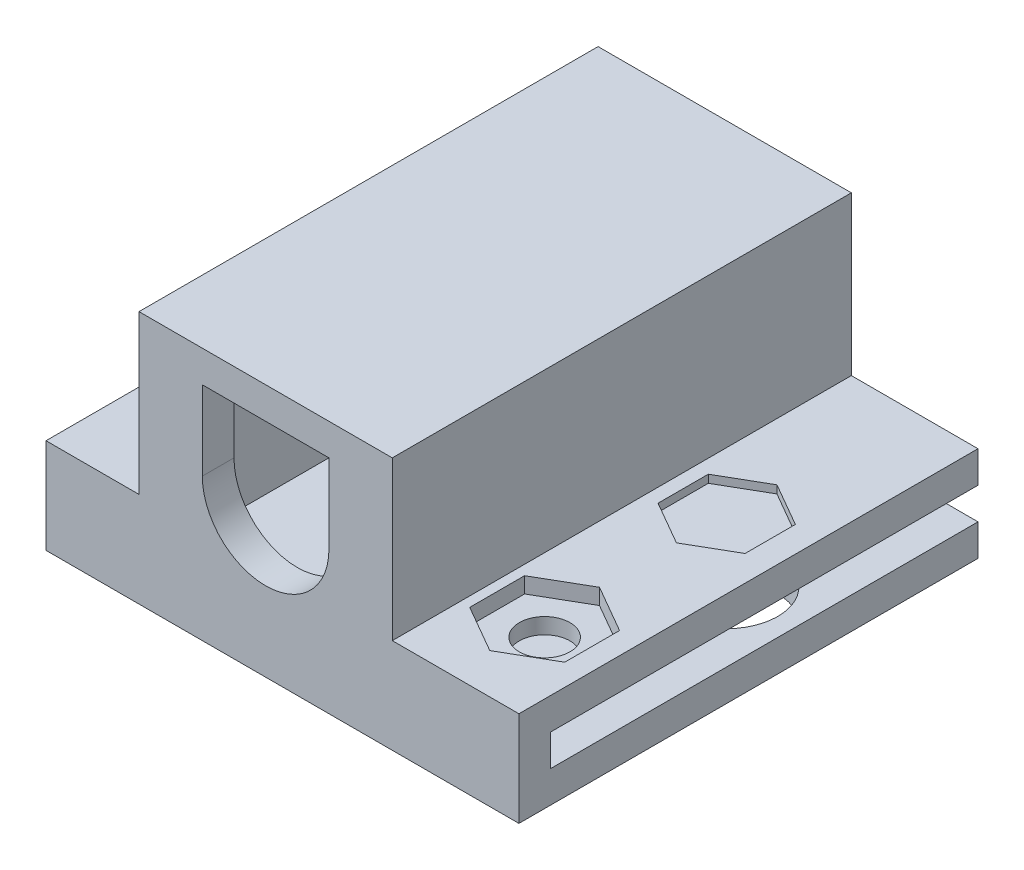
SolidWorks part; units mm, degrees
ref_plane "前视基准面" through (0, 0, 0) normal (0, 0, 1) x (1, 0, 0)
ref_plane "上视基准面" through (0, 0, 0) normal (0, 1, 0) x (1, 0, 0)
ref_plane "右视基准面" through (0, 0, 0) normal (1, 0, 0) x (0, 0, -1)
sketch "草图1" plane through (0, 0, 0) normal (0, 0, 1) x (1, 0, 0)
  line L1 (-13.875, -3) -> (-8, -3)
  line L2 (-13.875, -3) -> (-13.875, -9)
  line L3 (-13.875, -9) -> (16, -9)
  line L4 (5.5, 5) -> (-5.5, 5)
  line L5 (-6, 4.5) -> (-6, -4.5)
  line L6 (-5.5, -5) -> (5.5, -5)
  line L7 (6, -4.5) -> (6, 4.5)
  line L8 (5.5, 5) -> (-5.5, 5)
  line L9 (-6, 4.5) -> (-6, -4.5)
  line L10 (-5.5, -5) -> (5.5, -5)
  line L11 (6, -4.5) -> (6, 4.5)
  line L12 (-11.875, -7) -> (88.125, -7)
  line L13 (88.125, -7) -> (88.125, -5)
  line L14 (88.125, -5) -> (-11.875, -5)
  line L15 (-11.875, -5) -> (-11.875, -7)
  line L16 (-11.875, -7) -> (88.125, -7)
  line L17 (88.125, -7) -> (88.125, -5)
  line L18 (88.125, -5) -> (-11.875, -5)
  line L19 (-11.875, -5) -> (-11.875, -7)
  line L20 (16, -3) -> (16, -9)
  line L21 (-8, 7) -> (8, 7)
  line L22 (-8, 7) -> (-8, -3)
  line L23 (-8, -5) -> (8, -5)
  line L24 (8, 7) -> (8, -3)
  line L25 (8, -3) -> (16, -3)
  line L27 (0.8292, -1.25) -> (0.8292, 1.25)
  line L28 (0.8292, -1.25) -> (0.8292, 1.25)
  line L30 (-4, 0) -> (-4, 5)
  line L31 (-4, 5) -> (4, 5)
  line L32 (4, 0) -> (4, 5)
  arc A0 (-4, 0) -> (4, 0) centre (0, 0) ccw
  arc A1 (0.8292, 1.25) -> (0.8292, -1.25) centre (0, 0) ccw
  arc A2 (0.8292, 1.25) -> (0.8292, -1.25) centre (0, 0) ccw
  arc A4 (6, 4.5) -> (5.5, 5) centre (5.5, 4.5) ccw
  arc A5 (-5.5, 5) -> (-6, 4.5) centre (-5.5, 4.5) ccw
  arc A6 (-6, -4.5) -> (-5.5, -5) centre (-5.5, -4.5) ccw
  arc A7 (5.5, -5) -> (6, -4.5) centre (5.5, -4.5) ccw
  arc A8 (6, 4.5) -> (5.5, 5) centre (5.5, 4.5) ccw
  arc A9 (-5.5, 5) -> (-6, 4.5) centre (-5.5, 4.5) ccw
  arc A10 (-6, -4.5) -> (-5.5, -5) centre (-5.5, -4.5) ccw
  arc A11 (5.5, -5) -> (6, -4.5) centre (5.5, -4.5) ccw
  dimension "D11" = 8
  dimension "D3" = 2
  dimension "D4" = 2
  dimension "D5" = 2
  dimension "D6" = 2
  dimension "D7" = 2
  dimension "D8" = 8
  dimension "D9" = 2
  dimension "D1" = 0
  dimension "D2" = 0
  dimension "D10" = 0
extrude "凸台-拉伸1" add sketch "草图1" along normal blind 2 contours L10 A11 L11 A8 L8 L32 A0 L30 A9 L9 A10 | A11 L18 L20 L25 L24 L21 L22 L1 L2 L3 L16 L19 A10 L9 A9 L8 A8 L11 | L20 L18 L10 L19 L16 region at (-10.9375, -3.3389, 0) region at (2.0625, -6, 0) region at (0, -4.8438, 0)
sketch "草图2" plane through (0, 0, 0) normal (0, 0, -1) x (-1, 0, 0)
  line L0 (-88.125, -5) -> (11.875, -5) construction
  line L1 (-6, 5) -> (6, 5)
  line L2 (-6, 5) -> (-6, -5)
  line L4 (-6, 4.5) -> (-6, -4.5)
  line L5 (-5.5, -5) -> (5.5, -5)
  line L6 (6, -4.5) -> (6, 4.5)
  line L7 (5.5, 5) -> (-5.5, 5)
  line L8 (-16, -3) -> (-16, -9)
  line L9 (-16, -9) -> (13.875, -9)
  line L10 (13.875, -9) -> (13.875, -3)
  line L11 (13.875, -3) -> (8, -3)
  line L12 (8, -3) -> (8, 7)
  line L13 (8, 7) -> (-8, 7)
  line L14 (-8, 7) -> (-8, -3)
  line L15 (-8, -3) -> (-16, -3)
  line L16 (-16, -3) -> (-16, -9)
  line L17 (-16, -9) -> (13.875, -9)
  line L18 (13.875, -9) -> (13.875, -3)
  line L19 (13.875, -3) -> (8, -3)
  line L20 (8, -3) -> (8, 7)
  line L21 (8, 7) -> (-8, 7)
  line L22 (-8, 7) -> (-8, -3)
  line L23 (-8, -3) -> (-16, -3)
  line L24 (-6, 4.5) -> (-6, -4.5)
  line L26 (6, -4.5) -> (6, 4.5)
  line L27 (5.5, 5) -> (-5.5, 5)
  line L28 (6, 5) -> (6, -5)
  line L33 (-6, -5) -> (-88.125, -5)
  line L37 (-88.125, -7) -> (11.875, -7)
  line L38 (-88.125, -5) -> (-88.125, -7)
  line L39 (11.875, -5) -> (-88.125, -5)
  line L40 (11.875, -7) -> (11.875, -5)
  line L41 (-88.125, -7) -> (11.875, -7)
  line L42 (-88.125, -5) -> (-88.125, -7)
  line L43 (11.875, -5) -> (6, -5)
  line L44 (11.875, -7) -> (11.875, -5)
  arc A4 (-5.5, 5) -> (-6, 4.5) centre (-5.5, 4.5) ccw
  arc A5 (-6, -4.5) -> (-5.5, -5) centre (-5.5, -4.5) ccw
  arc A6 (5.5, -5) -> (6, -4.5) centre (5.5, -4.5) ccw
  arc A7 (6, 4.5) -> (5.5, 5) centre (5.5, 4.5) ccw
  arc A8 (-5.5, 5) -> (-6, 4.5) centre (-5.5, 4.5) ccw
  arc A11 (6, 4.5) -> (5.5, 5) centre (5.5, 4.5) ccw
  point P26 (6, 0)
  line M20 (-16, -3) -> (-16, -9)
  line M21 (-16, -9) -> (13.875, -9)
  line M22 (13.875, -9) -> (13.875, -3)
  line M23 (13.875, -3) -> (8, -3)
  line M24 (8, -3) -> (8, 7)
  line M25 (8, 7) -> (-8, 7)
  line M26 (-8, 7) -> (-8, -3)
  line M27 (-8, -3) -> (-16, -3)
  line M28 (-4, 5) -> (4, 5)
  dimension "D3" = 0
  dimension "D4" = 0
  dimension "D5" = 0
  dimension "D1" = 0
  dimension "D2" = 0
extrude "凸台-拉伸2" add sketch "草图2" along normal offset from surface (27 mm away) 2 contours L44 L41 L16 L43 L2 L1 L28 L26 M21 M22 M23 M24 M25 M26 M27 M20 M28 region at (6.3389, 4.75, 0) offset beyond the face yes
sketch "草图4" plane through (0, -9, 0) normal (0, -1, 0) x (1, 0, 0)
  line L0 (9.33, -14.175) -> (13.92, -16.825) construction
  line L2 (11.625, -18.7274) -> (14.42, -17.1137)
  line L3 (14.42, -17.1137) -> (14.42, -13.8863)
  line L4 (-13.875, 2) -> (-13.875, -27)
  line L5 (-13.875, -27) -> (16, -27)
  line L6 (16, -27) -> (16, 2)
  line L7 (16, 2) -> (-13.875, 2)
  line L8 (-13.875, 2) -> (-13.875, -27)
  line L10 (16, -27) -> (16, 2)
  line L11 (16, 2) -> (-13.875, 2)
  line L12 (14.42, -13.8863) -> (11.625, -12.2726)
  line L13 (11.625, -12.2726) -> (8.83, -13.8863)
  line L14 (9.33, -14.175) -> (9.33, -16.825)
  line L15 (9.33, -16.825) -> (11.625, -18.15)
  line L16 (11.625, -18.15) -> (13.92, -16.825)
  line L17 (13.92, -16.825) -> (13.92, -14.175)
  line L18 (13.92, -14.175) -> (11.625, -12.85)
  line L19 (11.625, -12.85) -> (9.33, -14.175)
  line L20 (9.33, -14.175) -> (9.33, -16.825)
  line L21 (9.33, -16.825) -> (11.625, -18.15)
  line L22 (11.625, -18.15) -> (13.92, -16.825)
  line L23 (13.92, -16.825) -> (13.92, -14.175)
  line L24 (13.92, -14.175) -> (11.625, -12.85)
  line L25 (11.625, -12.85) -> (9.33, -14.175)
  line L26 (8.83, -13.8863) -> (8.83, -17.1137)
  line L27 (8.83, -17.1137) -> (11.625, -18.7274)
  line L31 (-13.875, -27) -> (16, -27)
  circle A0 centre (11.625, -15.5) radius 2.795 construction
  circle A1 centre (11.625, -15.5) radius 3.2274
  dimension "D3" = 0.5
  dimension "D1" = 0
  dimension "D2" = 0
extrude "切除-拉伸1" cut sketch "草图4" against normal blind 2 contours A1
sketch "草图5" plane through (0, -3, 0) normal (0, 1, 0) x (1, 0, 0)
  line L1 (11.625, 18.6754) -> (8.875, 17.0877)
  line L2 (8.875, 17.0877) -> (8.875, 13.9123)
  line L3 (8.875, 13.9123) -> (11.625, 12.3246)
  line L4 (16, -2) -> (16, 27)
  line L5 (16, 27) -> (8, 27)
  line L6 (8, 27) -> (8, -2)
  line L7 (8, -2) -> (16, -2)
  line L8 (16, -2) -> (16, 27)
  line L10 (8, 27) -> (8, -2)
  line L11 (8, -2) -> (16, -2)
  line L12 (11.625, 12.3246) -> (14.375, 13.9123)
  line L13 (14.375, 13.9123) -> (14.375, 17.0877)
  line L14 (14.375, 17.0877) -> (11.625, 18.6754)
  line L18 (16, 27) -> (8, 27)
  circle A0 centre (11.625, 15.5) radius 3
  circle A1 centre (11.625, 15.5) radius 1.25
  circle A2 centre (11.625, 15.5) radius 1.25
  circle A3 centre (11.625, 15.5) radius 2.75 construction
  dimension "D3" = 5.5
  dimension "D1" = 0
  dimension "D2" = 0
extrude "切除-拉伸2" cut sketch "草图5" against normal blind 0.5 contours L14 L1 L2 L3 L12 L13
sketch "草图6" plane through (0, -3, 0) normal (0, 1, 0) x (1, 0, 0)
  line L0 (11.625, 18.6754) -> (11.625, -2) construction
  line L2 (14.625, 2.2679) -> (14.625, 5.7321)
  line L3 (14.625, 5.7321) -> (11.625, 7.4641)
  line L4 (16, -2) -> (16, 27)
  line L5 (16, 27) -> (8, 27)
  line L6 (8, 27) -> (8, -2)
  line L7 (8, -2) -> (16, -2)
  line L8 (16, -2) -> (16, 27)
  line L10 (8, 27) -> (8, -2)
  line L11 (8, -2) -> (16, -2)
  line L12 (11.625, 7.4641) -> (8.625, 5.7321)
  line L13 (8.625, 5.7321) -> (8.625, 2.2679)
  line L14 (14.375, 13.9123) -> (14.375, 17.0877)
  line L15 (14.375, 17.0877) -> (11.625, 18.6754)
  line L16 (11.625, 18.6754) -> (8.875, 17.0877)
  line L17 (8.875, 17.0877) -> (8.875, 13.9123)
  line L18 (8.875, 13.9123) -> (11.625, 12.3246)
  line L19 (11.625, 12.3246) -> (14.375, 13.9123)
  line L20 (14.375, 13.9123) -> (14.375, 17.0877)
  line L21 (14.375, 17.0877) -> (11.625, 18.6754)
  line L22 (11.625, 18.6754) -> (8.875, 17.0877)
  line L23 (8.875, 17.0877) -> (8.875, 13.9123)
  line L24 (8.875, 13.9123) -> (11.625, 12.3246)
  line L25 (11.625, 12.3246) -> (14.375, 13.9123)
  line L26 (8.625, 2.2679) -> (11.625, 0.5359)
  line L27 (11.625, 0.5359) -> (14.625, 2.2679)
  line L31 (16, 27) -> (8, 27)
  circle A0 centre (11.625, 4) radius 3 construction
  dimension "D3" = 6
  dimension "D4" = 6
  dimension "D1" = 0
  dimension "D2" = 0
extrude "切除-拉伸3" cut sketch "草图6" against normal blind 1 contours L26 L27 L2 L3 L12 L13 region at (11.625, -3, -4)
sketch "草图7" plane through (0, -4, 0) normal (0, 1, 0) x (1, 0, 0)
  line L0 (11.625, 7.4641) -> (11.625, 0.5359) construction
  line L6 (8.625, 2.2679) -> (11.625, 0.5359)
  line L7 (11.625, 0.5359) -> (14.625, 2.2679)
  line L8 (14.625, 2.2679) -> (14.625, 5.7321)
  line L9 (14.625, 5.7321) -> (11.625, 7.4641)
  line L10 (11.625, 7.4641) -> (8.625, 5.7321)
  line L11 (8.625, 5.7321) -> (8.625, 2.2679)
  line L12 (8.625, 2.2679) -> (11.625, 0.5359)
  line L13 (11.625, 0.5359) -> (14.625, 2.2679)
  line L14 (14.625, 2.2679) -> (14.625, 5.7321)
  line L15 (14.625, 5.7321) -> (11.625, 7.4641)
  line L16 (11.625, 7.4641) -> (8.625, 5.7321)
  line L17 (8.625, 5.7321) -> (8.625, 2.2679)
  circle A0 centre (11.625, 4) radius 1.6
  dimension "D2" = 3.2
  dimension "D1" = 0
extrude "切除-拉伸4" cut sketch "草图7" against normal through all contours L0 A0 | A0 L0 region at (12.3041, -4, -4) region at (10.9459, -4, -4)
sketch "草图8" plane through (0, 0, -27) normal (0, 0, -1) x (-1, 0, 0)
  line L0 (6, -5) -> (6, 5) construction
  line L1 (-6, 5) -> (6, 5)
  line L2 (-6, 5) -> (-6, 4)
  line L3 (-6, 4) -> (6, 4)
  line L4 (6, 5) -> (6, 4)
  dimension "D1" = 1
extrude "凸台-拉伸3" add sketch "草图8" against normal blind 1.6
